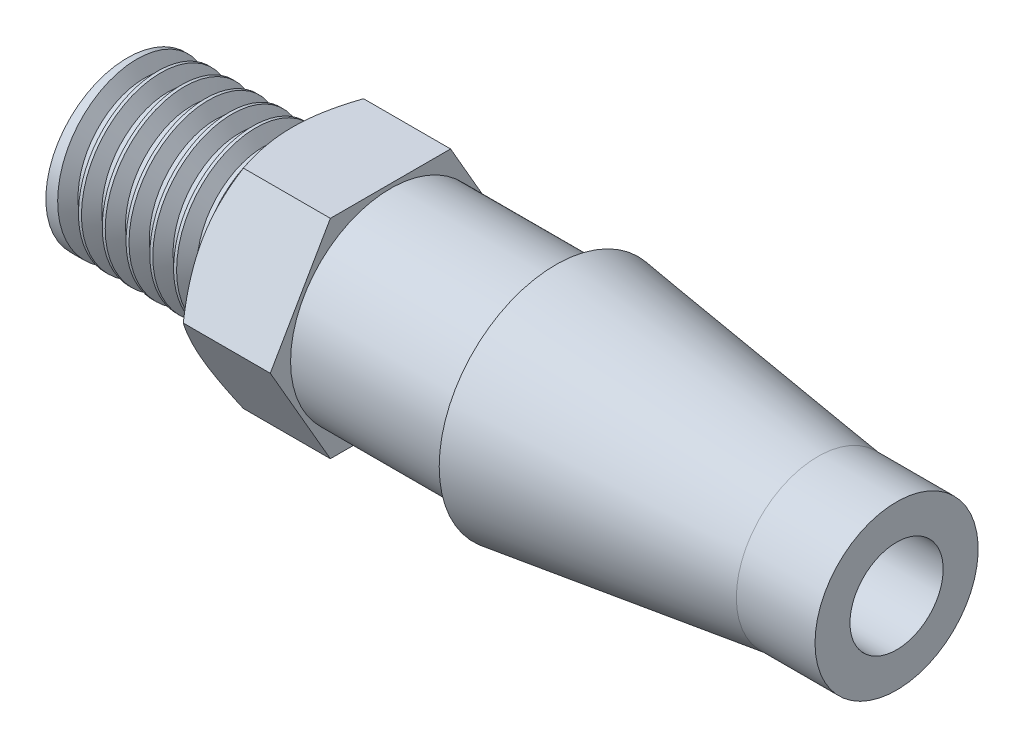
SolidWorks part; units mm, degrees
ref_plane "Front Plane" through (0, 0, 0) normal (0, 0, 1) x (1, 0, 0)
ref_plane "Top Plane" through (0, 0, 0) normal (0, 1, 0) x (1, 0, 0)
ref_plane "Right Plane" through (0, 0, 0) normal (1, 0, 0) x (0, 0, -1)
sketch "Sketch1" plane through (0, 0, 0) normal (0, 0, 1) x (1, 0, 0)
  line L0 (-14.6981, 0) -> (24.5872, 0) construction
  line L1 (0, 1.778) -> (29.337, 1.778)
  line L2 (29.337, 1.778) -> (29.337, 3.1115)
  line L3 (29.337, 3.1115) -> (26.337, 3.1115)
  line L4 (26.337, 3.1115) -> (16.337, 4.445)
  line L5 (16.337, 4.445) -> (16.337, 3.81)
  line L6 (16.337, 3.81) -> (10.033, 3.81)
  line L7 (10.033, 3.81) -> (10.033, 4.5847)
  line L8 (10.033, 4.5847) -> (6.715, 4.5847)
  line L9 (6.715, 4.5847) -> (5.715, 3.1115)
  line L10 (5.715, 3.1115) -> (0, 3.1115)
  line L11 (0, 3.1115) -> (0, 1.778)
  point P10 (10.9728, 8.89)
  point P15 (12.5287, 4.445)
  point P16 (-2.3237, 3.81)
  point P17 (10.8106, 3.81)
  point P18 (8.4711, 3.81)
  point P19 (16.069, 4.445)
  point P20 (23.6597, 3.1115)
  point P21 (15.8367, 3.81)
  point P22 (26.5685, 3.1115)
  point P23 (0, 0)
  point P24 (6.6947, 4.5847)
  point P25 (10.033, 3.81)
  point P26 (7.149, 4.5847)
  point P27 (0, 0)
  point P28 (0, 0)
  point P29 (6.4676, 4.5847)
  dimension "D1" = 1.778
  dimension "D2" = 4.445
  dimension "D3" = 4.5847
  dimension "D4" = 3.1115
  dimension "D5" = 5.715
  dimension "D6" = 19.304
  dimension "D7" = 3.81
  dimension "D8" = 29.337
  dimension "D9" = 1
  dimension "D10" = 3
  dimension "D11" = 10
revolve "Revolve1" add sketch "Sketch1" angle 360 about L0
sketch "Sketch2" plane through (10.033, 0, 0) normal (1, 0, 0) x (0, 0, -1)
  line L0 (-2.2923, 3.9705) -> (2.2923, 3.9705)
  line L1 (2.2923, 3.9705) -> (4.5847, 0)
  line L2 (4.5847, 0) -> (2.2923, -3.9705)
  line L3 (2.2923, -3.9705) -> (-2.2923, -3.9705)
  line L4 (-2.2923, -3.9705) -> (-4.5847, 0)
  line L5 (-4.5847, 0) -> (-2.2923, 3.9705)
  circle A0 centre (0, 0) radius 4.5847 construction
  point P7 (2.597, 3.7782)
extrude "Cut-Extrude-Thin1" cut sketch "Sketch2" against normal blind 10 flip side to cut thin thin type one direction wall 10
thread "Thread1" pitch 0.9071 method cut profile "Thread Profile1" start angle 0, offset 0, length 0, pitch 0.9071, diameter 6.223
ref_plane "Plane1" through (0, 0, -3.1115) normal (0, -1, 0) x (0, 0, -1)
sketch "Thread Profile1" plane through (0, 0, -3.1115) normal (0, -1, 0) x (0, 0, -1)
  line L0 (0, 0) -> (0, 0.9071) construction
  line L11 (0, 0) -> (0, 0.7937)
  line L12 (0, 0.7937) -> (-0.491, 0.5103)
  line L13 (-0.491, 0.5103) -> (-0.491, 0.2835)
  line L15 (-0.491, 0.2835) -> (0, 0)
  line L17 (-0.491, 0.3969) -> (0, 0.3969) construction
  point P2 (0, 0)
  dimension "Pitch" = 0.9071
  dimension "Profile_Angle" = 60
  dimension "Profile_Land" = 0.2268
  dimension "Profile_Height" = 0.491
